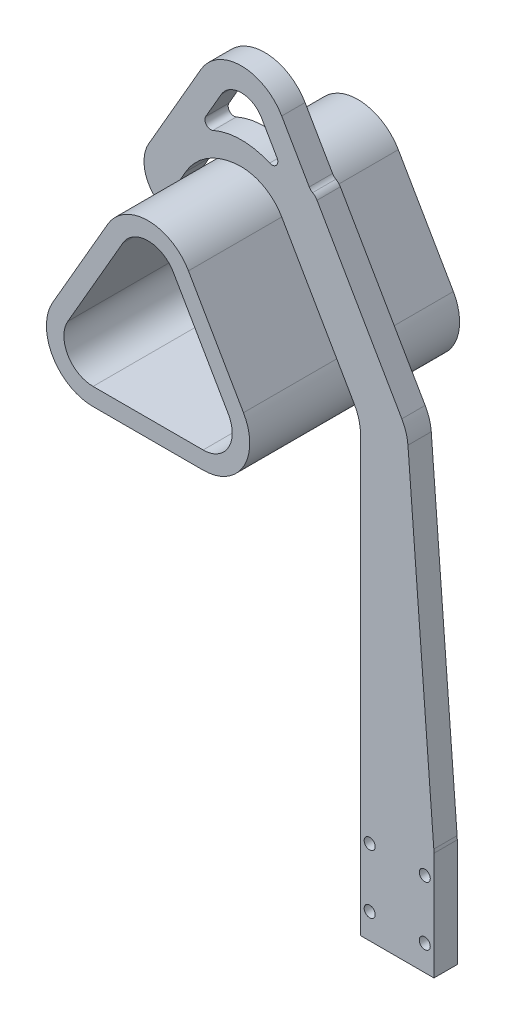
SolidWorks part; units mm, degrees
ref_plane "Front Plane" through (0, 0, 0) normal (0, 0, 1) x (1, 0, 0)
ref_plane "Top Plane" through (0, 0, 0) normal (0, 1, 0) x (1, 0, 0)
ref_plane "Right Plane" through (0, 0, 0) normal (1, 0, 0) x (0, 0, -1)
sketch "Sketch1" plane through (0, 0, 0) normal (0, 0, 1) x (1, 0, 0)
  line L0 (0, 0) -> (0, 29.9)
  line L1 (0, 29.9) -> (-7.3, 124.9982)
  line L2 (0, 0) -> (-20, 0)
  line L3 (-20, 0) -> (-20, 121.5953)
  line L4 (-20, 121.5953) -> (-41.4513, 158.75)
  line L6 (-37.4625, 113.7412) -> (-67.4371, 113.7412) construction
  line L8 (-41.4513, 182.5625) -> (-33.9576, 169.5831)
  line L9 (-73.0042, 146.9612) -> (-52.4498, 152.4) construction
  line L11 (-24.7625, 126.4412) -> (-24.7625, 52.4186) construction
  line L12 (-63.4483, 158.75) -> (-78.4357, 132.7912) construction
  line L13 (-67.5728, 156.3687) -> (-71.8136, 149.0234)
  line L14 (-63.4483, 182.5625) -> (-77.6812, 157.9104)
  line L15 (-37.4625, 126.4412) -> (-92.5926, 158.2706) construction
  line L16 (-52.4498, 176.2125) -> (-31.8954, 170.7737) construction
  line L17 (-32.5117, 168.4736) -> (-32.3802, 168.4384)
  line L18 (-32.3802, 168.4384) -> (-7.3, 124.9982)
  line L19 (0, 0) -> (-2.5, 6.95) construction
  line L20 (-17.5, 22.95) -> (-2.5, 22.95) construction
  line L21 (-17.5, 22.95) -> (-17.5, 6.95) construction
  line L22 (-17.5, 6.95) -> (-2.5, 6.95) construction
  line L23 (-2.5, 22.95) -> (-2.5, 6.95) construction
  line L24 (-17.5, 22.95) -> (-20, 29.9) construction
  line L25 (-17.5, 6.95) -> (-20, 0) construction
  arc A3 (-26.464, 132.7912) -> (-37.4625, 113.7412) centre (-37.4625, 126.4412) cw construction
  arc A8 (-41.4513, 158.75) -> (-52.4498, 165.1) centre (-52.4498, 152.4) ccw
  arc A9 (-52.4498, 165.1) -> (-63.4483, 158.75) centre (-52.4498, 152.4) ccw construction
  arc A10 (-52.4498, 165.1) -> (-67.5728, 156.3687) centre (-52.4498, 147.6375) ccw
  arc A11 (-71.8136, 149.0234) -> (-74.1949, 144.899) centre (-73.0042, 146.9612) cw
  arc A12 (-63.4483, 182.5625) -> (-41.4513, 182.5625) centre (-52.4498, 176.2125) cw
  arc A13 (-74.1949, 144.899) -> (-77.6812, 157.9104) centre (-69.4324, 153.1479) cw
  arc A14 (-78.4357, 132.7912) -> (-67.4371, 113.7412) centre (-67.4371, 126.4412) ccw construction
  circle A15 centre (-31.8954, 170.7737) radius 2.3813 construction
  arc A16 (-33.9576, 169.5831) -> (-32.5117, 168.4736) centre (-31.8954, 170.7737) ccw
  circle A17 centre (-2.5, 22.95) radius 1.5
  circle A18 centre (-2.5, 6.95) radius 1.5
  circle A19 centre (-17.5, 6.95) radius 1.5
  circle A20 centre (-17.5, 22.95) radius 1.5
  point P13 (-70.942, 145.7706)
  dimension "D1" = 20
  dimension "D4" = 12.7
  dimension "D5" = 60
  dimension "D7" = 9.525
  dimension "D8" = 9.525
  dimension "D9" = 2.3813
  dimension "D10" = 12.7
  dimension "D16" = 3
  dimension "D2" = 29.9
  dimension "D3" = 150
  dimension "D6" = 38.6588
  dimension "D11" = 45
  dimension "D12" = 12.7
  dimension "D13" = 152.4
  dimension "D14" = 16
  dimension "D15" = 15
extrude "Boss-Extrude1" add sketch "Sketch1" along normal blind 6.35
fillet "Fillet1" radius 3.175 2 edges at (-32.3802, 168.4384, 3.175) (-71.8136, 149.0234, 3.175)
fillet "Fillet2" radius 12.7 3 edges at (0, 29.9, 3.175) (-7.3, 124.9982, 3.175) (-20, 121.5953, 3.175)
sketch "Sketch2" plane through (0, 0, 6.35) normal (0, 0, 1) x (1, 0, 0)
  line L4 (-57.9491, 179.3875) -> (-65.5394, 166.2408)
  line L5 (-46.9506, 179.3875) -> (-39.3603, 166.2408)
  line L6 (-63.4483, 182.5625) -> (-77.6812, 157.9104) construction
  line L7 (-33.9576, 169.5831) -> (-41.4513, 182.5625) construction
  arc A4 (-65.5394, 166.2408) -> (-39.3603, 166.2408) centre (-52.4498, 152.4) cw
  arc A5 (-57.9491, 179.3875) -> (-46.9506, 179.3875) centre (-52.4498, 176.2125) cw
  arc A6 (-41.4513, 158.75) -> (-52.4498, 165.1) centre (-52.4498, 152.4) ccw construction
  arc A7 (-41.4513, 182.5625) -> (-63.4483, 182.5625) centre (-52.4498, 176.2125) ccw construction
  dimension "D1" = 6.35
  dimension "D2" = 6.35
extrude "Cut-Extrude1" cut sketch "Sketch2" against normal up to next
fillet "Fillet3" radius 1.5875 2 edges at (-65.5394, 166.2408, 3.175) (-39.3603, 166.2408, 3.175)
sketch "Sketch3" plane through (0, 0, 6.35) normal (0, 0, 1) x (1, 0, 0)
  line L0 (-41.4513, 158.75) -> (-21.7015, 124.5423) construction
  line L1 (-41.4513, 158.75) -> (-26.464, 132.7912)
  line L2 (-63.4483, 158.75) -> (-78.4357, 132.7912)
  line L3 (-67.4371, 113.7412) -> (-37.4625, 113.7412)
  line L4 (-67.4371, 118.5037) -> (-37.4625, 118.5037)
  line L5 (-45.5757, 156.3688) -> (-30.5884, 130.4099)
  line L6 (-59.3239, 156.3687) -> (-74.3112, 130.4099)
  arc A0 (-41.4513, 158.75) -> (-52.4498, 165.1) centre (-52.4498, 152.4) ccw construction
  arc A1 (-41.4513, 158.75) -> (-63.4483, 158.75) centre (-52.4498, 152.4) ccw
  arc A2 (-78.4357, 132.7912) -> (-67.4371, 113.7412) centre (-67.4371, 126.4412) ccw
  arc A3 (-26.464, 132.7912) -> (-37.4625, 113.7412) centre (-37.4625, 126.4412) cw
  arc A4 (-30.5884, 130.4099) -> (-37.4625, 118.5037) centre (-37.4625, 126.4412) cw
  arc A5 (-45.5757, 156.3688) -> (-59.3239, 156.3687) centre (-52.4498, 152.4) ccw
  arc A6 (-74.3112, 130.4099) -> (-67.4371, 118.5037) centre (-67.4371, 126.4412) ccw
  point P9 (-67.4702, 105.0188)
  point P11 (-30.605, 82.5601)
  dimension "D1" = 38.6588
  dimension "D2" = 4.7625
extrude "Boss-Extrude2" add sketch "Sketch3" along normal blind 25.4 and the other way blind 31.75 separate body
